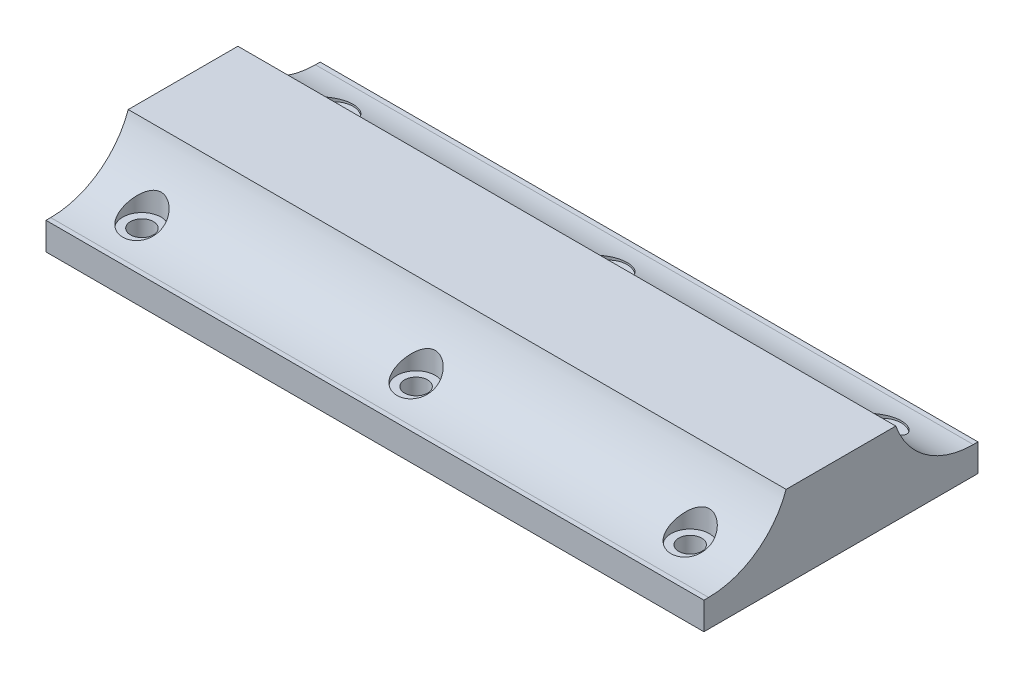
SolidWorks part; units mm, degrees
ref_plane "Front Plane" through (0, 0, 0) normal (0, 0, 1) x (1, 0, 0)
ref_plane "Top Plane" through (0, 0, 0) normal (0, 1, 0) x (1, 0, 0)
ref_plane "Right Plane" through (0, 0, 0) normal (1, 0, 0) x (0, 0, -1)
sketch "Sketch2" plane through (0, 0, 0) normal (0, 1, 0) x (1, 0, 0)
  line L0 (-46.8981, 34.5466) -> (-46.8981, -15.4534)
  line L1 (-46.8981, -15.4534) -> (73.1019, -15.4534)
  line L2 (73.1019, -15.4534) -> (73.1019, 34.5466)
  line L3 (73.1019, 34.5466) -> (-46.8981, 34.5466)
  dimension "D1" = 120
  dimension "D2" = 50
extrude "Boss-Extrude1" add sketch "Sketch2" along normal blind 15
sketch "Sketch3" plane through (0, 0, 0) normal (0, 1, 0) x (1, 0, 0)
  line L0 (74.3548, 9.5466) -> (-56.2815, 9.5466) construction
  line L1 (63.1019, 9.5466) -> (63.1019, 17.0466)
  line L2 (63.1019, 17.0466) -> (3.1019, 17.0466)
  line L3 (3.1019, 17.0466) -> (3.1019, 19.5466)
  line L4 (3.1019, 19.5466) -> (-36.8981, 19.5466)
  line L5 (-36.8981, 19.5466) -> (-36.8981, 9.5466)
  line L6 (-36.8981, 9.5466) -> (63.1019, 9.5466)
  line L7 (73.1019, -15.4534) -> (73.1019, 34.5466) construction
  line L9 (-46.8981, -15.4534) -> (73.1019, -15.4534) construction
  dimension "D1" = 60
  dimension "D2" = 40
  dimension "D3" = 10
  dimension "D4" = 25
  dimension "D5" = 10
  dimension "D6" = 7.5
sketch "Skizze7" plane through (-46.8981, 0, 0) normal (-1, 0, 0) x (0, 0, 1)
  line L1 (-34.5466, 0) -> (15.4534, 0) construction
  line L3 (-9.5466, -6.0172) -> (-9.5466, 6.0172) construction
  line L4 (15.4534, 15) -> (15.4534, 0) construction
  line L5 (-34.5466, 15) -> (-34.5466, 0) construction
  circle A0 centre (-9.5466, 2.5) radius 1.5
  dimension "D1" = 3
  dimension "D2" = 2.5
extrude "Schnitt-Linear austragen6" cut sketch "Skizze7" against normal blind 10
revolve "Schnitt-Rotation1" cut sketch "Sketch3" angle 360 about L0
sketch "Skizze10" plane through (0, 0, 0) normal (0, -1, 0) x (1, 0, 0)
  line L0 (63.1019, -17.0466) -> (3.1019, -17.0466) construction
  line L1 (53.1019, -17.0466) -> (40.6019, -17.0466)
  line L2 (53.1019, -17.0466) -> (53.1019, -14.5466)
  line L3 (53.1019, -14.5466) -> (40.6019, -14.5466)
  line L4 (40.6019, -17.0466) -> (40.6019, -14.5466)
  line L5 (63.1019, -2.0466) -> (63.1019, -17.0466) construction
  line L10 (85.7448, -9.5466) -> (-66.8579, -9.5466) construction
  line L11 (-46.8981, 15.4534) -> (73.1019, 15.4534) construction
  line L12 (73.1019, -34.5466) -> (-46.8981, -34.5466) construction
  dimension "D1" = 10
  dimension "D2" = 12.5
  dimension "D5" = 2.5
revolve "Rotation3" add sketch "Skizze10" angle 180 about L10 reverse direction yes
sketch "Skizze11" plane through (0, 0, 0) normal (0, -1, 0) x (1, 0, 0)
  line L0 (40.6019, -17.0466) -> (3.1019, -17.0466) construction
  line L1 (28.1019, -17.0466) -> (15.6019, -17.0466)
  line L2 (28.1019, -17.0466) -> (28.1019, -14.5466)
  line L3 (28.1019, -14.5466) -> (15.6019, -14.5466)
  line L4 (15.6019, -17.0466) -> (15.6019, -14.5466)
  line L5 (53.1019, -14.5466) -> (40.6019, -14.5466) construction
  line L6 (40.6019, -14.5466) -> (40.6019, -17.0466) construction
  line L7 (95.0378, -9.5466) -> (-94.5432, -9.5466) construction
  line L8 (-46.8981, 15.4534) -> (73.1019, 15.4534) construction
  line L9 (73.1019, -34.5466) -> (-46.8981, -34.5466) construction
  point P10 (40.6019, -15.7966)
  dimension "D1" = 12.5
  dimension "D2" = 12.5
revolve "Rotation4" add sketch "Skizze11" angle 180 about L7 reverse direction yes
sketch "Skizze12" plane through (0, 0, 0) normal (0, -1, 0) x (1, 0, 0)
  line L0 (73.1019, 15.4534) -> (73.1019, -34.5466) construction
  line L1 (-46.8981, -34.5466) -> (-46.8981, 15.4534) construction
  line L3 (-46.8981, 15.4534) -> (73.1019, 15.4534) construction
  circle A0 centre (-36.8981, 7.9534) radius 2.1
  circle A1 centre (13.1019, 7.9534) radius 2.1
  circle A2 centre (63.1019, 7.9534) radius 2.1
  dimension "D3" = 4.2
  dimension "D2" = 10
  dimension "D4" = 10
  dimension "D5" = 7.5
  dimension "D1" = 3
ref_plane "Ebene6" through (0, 0, -9.5466) normal (0, 0, 1) x (1, 0, 0)
extrude "Schnitt-Linear austragen7" cut sketch "Skizze12" against normal through all
mirror "Spiegeln1" about plane through (0, 0, -9.5466) normal (0, 0, 1) of "Schnitt-Linear austragen7"
sketch "Skizze13" plane through (-46.8981, 0, 0) normal (-1, 0, 0) x (0, 0, 1)
  line L0 (-34.5466, 0) -> (15.4534, 0) construction
  line L1 (15.4534, 15) -> (0.4534, 15)
  line L2 (15.4534, 15) -> (15.4534, 5)
  line L3 (15.4534, 5) -> (0.4534, 5)
  line L4 (0.4534, 15) -> (0.4534, 5)
  line L5 (-34.5466, 0) -> (15.4534, 0) construction
  line L6 (-34.5466, 15) -> (-19.5466, 15)
  line L7 (-34.5466, 15) -> (-34.5466, 5)
  line L8 (-34.5466, 5) -> (-19.5466, 5)
  line L9 (-19.5466, 15) -> (-19.5466, 5)
  dimension "D1" = 15
  dimension "D2" = 5
  dimension "D3" = 15
  dimension "D4" = 5
extrude "Schnitt-Linear austragen8" cut sketch "Skizze13" against normal through all contours L2 L1 L4 L3 | L7 L6 L9 L8
fillet "Fillet7" radius 15 1 edges at (13.1019, 5, 0.4534)
fillet "Fillet8" radius 15 1 edges at (13.1019, 5, -19.5466)
ref_plane "Plane1" through (0, 25, 0) normal (0, 1, 0) x (1, 0, 0)
sketch "Sketch7" plane through (0, 25, 0) normal (0, 1, 0) x (1, 0, 0)
  circle A0 centre (13.1019, 27.0466) radius 3.5
  circle A1 centre (63.1019, 27.0466) radius 3.5
  circle A2 centre (63.1019, -7.9534) radius 3.5
  circle A3 centre (13.1019, -7.9534) radius 3.5
  circle A4 centre (-36.8981, -7.9534) radius 3.5
  circle A5 centre (-36.8981, 27.0466) radius 3.5
  dimension "D1" = 7
  dimension "D2" = 7
  dimension "D3" = 7
  dimension "D4" = 7
  dimension "D5" = 7
  dimension "D6" = 7
extrude "Cut-Extrude2" cut sketch "Sketch7" against normal blind 20
